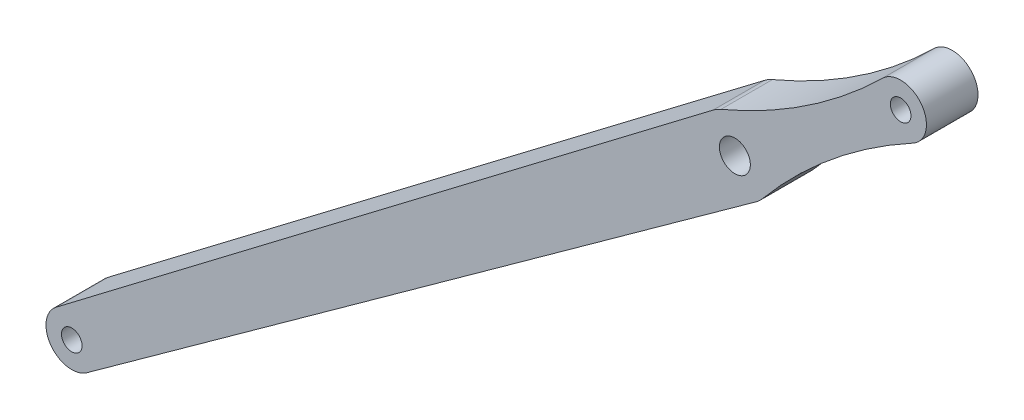
SolidWorks part; units mm, degrees
ref_plane "Front Plane" through (0, 0, 0) normal (0, 0, 1) x (1, 0, 0)
ref_plane "Top Plane" through (0, 0, 0) normal (0, 1, 0) x (1, 0, 0)
ref_plane "Right Plane" through (0, 0, 0) normal (1, 0, 0) x (0, 0, -1)
sketch "Sketch1" plane through (0, 0, 0) normal (0, 0, 1) x (1, 0, 0)
  line L0 (-98.2744, 131.3077) -> (-228.0381, 37.7268) construction
  line L3 (-106.604, 142.5588) -> (-233.9878, 45.7633) construction
  line L4 (-98.2744, 131.3077) -> (-228.0381, 37.7268)
  line L5 (-106.604, 142.5588) -> (-233.9878, 45.7633)
  arc A5 (-67.8372, 156.3906) -> (-96.9916, 132.5037) centre (-20.1733, 68.4807) ccw construction
  arc A6 (-105.0857, 143.4366) -> (-73.7288, 164.3485) centre (-143.8967, 235.5979) ccw construction
  circle A13 centre (-70.2204, 160.7861) radius 5 construction
  circle A14 centre (-230.9627, 41.7822) radius 5 construction
  circle A15 centre (-102.3689, 136.9853) radius 7 construction
  circle A16 centre (-70.2204, 160.7861) radius 2 construction
  circle A17 centre (-102.3689, 136.9853) radius 3 construction
  circle A18 centre (-230.9627, 41.7822) radius 2 construction
  arc A19 (-67.8372, 156.3906) -> (-96.9916, 132.5037) centre (-20.1733, 68.4807) ccw
  arc A20 (-105.0857, 143.4366) -> (-73.7288, 164.3485) centre (-143.8967, 235.5979) ccw
  circle A21 centre (-70.2204, 160.7861) radius 5
  circle A22 centre (-230.9627, 41.7822) radius 5
  circle A23 centre (-102.3689, 136.9853) radius 7
  circle A24 centre (-70.2204, 160.7861) radius 2
  circle A25 centre (-102.3689, 136.9853) radius 3
  circle A26 centre (-230.9627, 41.7822) radius 2
extrude "Boss-Extrude1" add sketch "Sketch1" along normal blind 5 and the other way blind 5 contours A23 L5 A22 L4 | A22 A26 | A21 A24 | A23 A19 A21 A20 | A23 A25 region at (-164.1425, 91.2518, 0) region at (-107.8357, 132.938, 0) region at (-234.8676, 38.8913, 0) region at (-86.1743, 148.9748, 0) region at (-74.1253, 157.8951, 0)
